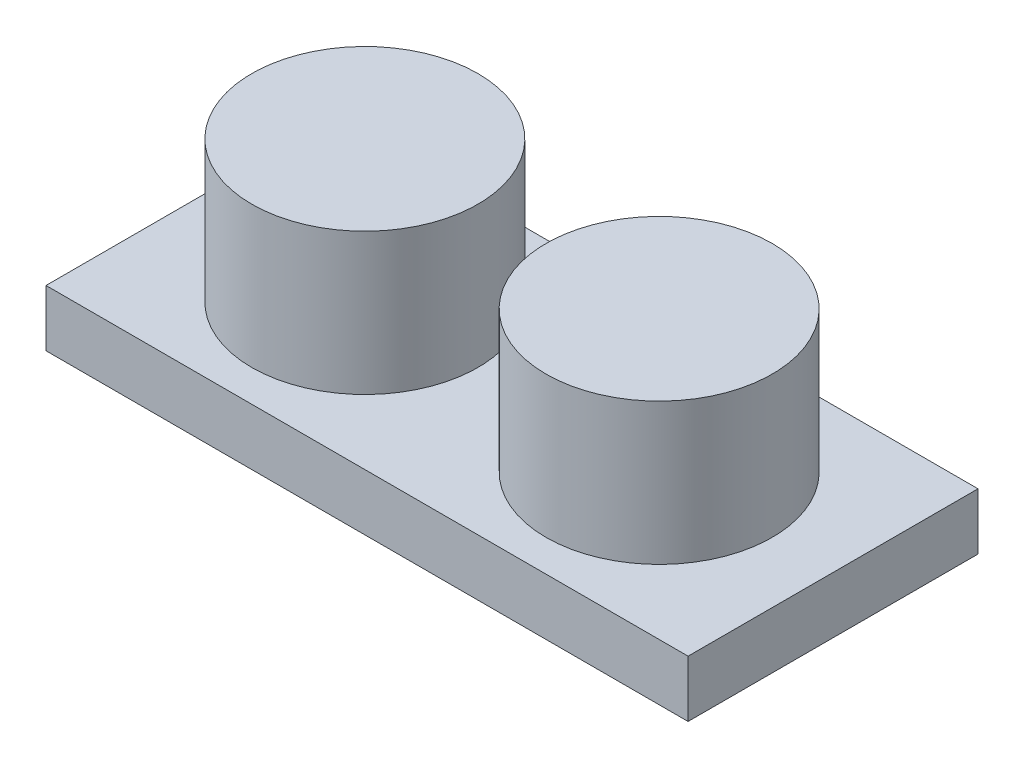
SolidWorks part; units mm, degrees
ref_plane "前基準面" through (0, 0, 0) normal (0, 0, 1) x (1, 0, 0)
ref_plane "上基準面" through (0, 0, 0) normal (0, 1, 0) x (1, 0, 0)
ref_plane "右基準面" through (0, 0, 0) normal (1, 0, 0) x (0, 0, -1)
sketch "草圖1" plane through (0, 0, 0) normal (0, 1, 0) x (1, 0, 0)
  line L0 (0, 10.25) -> (0, -10.25) construction
  line L1 (-22.7, 10.25) -> (22.7, 10.25)
  line L2 (-22.7, 10.25) -> (-22.7, -10.25)
  line L3 (-22.7, -10.25) -> (22.7, -10.25)
  line L4 (22.7, 10.25) -> (22.7, -10.25)
  line L5 (-22.7, 10.25) -> (22.7, -10.25) construction
  line L6 (-22.7, -10.25) -> (22.7, 10.25) construction
  circle A0 centre (-10.4042, 0) radius 8
  circle A1 centre (10.4042, 0) radius 8
  point P0 (0, 0)
  dimension "D1" = 45.4
  dimension "D2" = 20.5
extrude "填料-伸長3" add sketch "草圖1" along normal blind 4 contours L4 L1 L2 L3 A0 A1 | A0 | A1 region at (0, 0, 0)
extrude "填料-伸長4" add sketch "草圖1<5>" along normal blind 14 contours A0 | A1 region at (-10.4042, 0, 0) region at (10.4042, 0, 0)
sketch "草圖1<5>" plane through (0, 0, 0) normal (0, 1, 0) x (1, 0, 0) same geometry as "草圖1"
